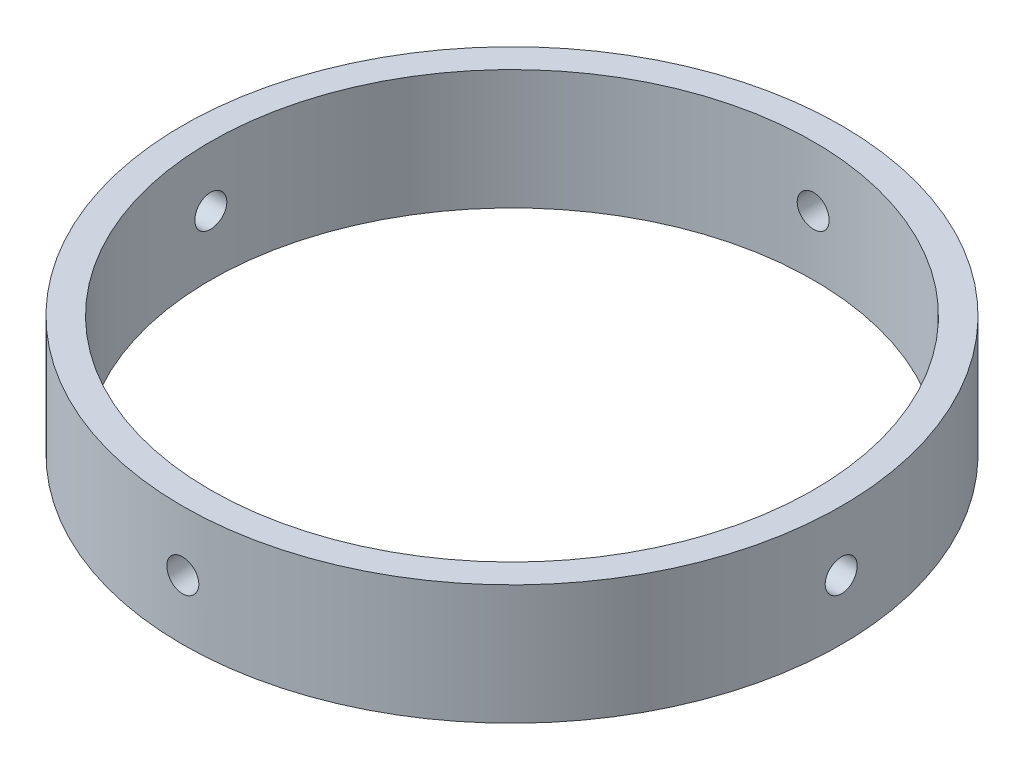
SolidWorks part; units mm, degrees
ref_plane "Front Plane" through (0, 0, 0) normal (0, 0, 1) x (1, 0, 0)
ref_plane "Top Plane" through (0, 0, 0) normal (0, 1, 0) x (1, 0, 0)
ref_plane "Right Plane" through (0, 0, 0) normal (1, 0, 0) x (0, 0, -1)
sketch "Sketch1" plane through (0, 0, 0) normal (0, 1, 0) x (1, 0, 0)
  line L0 (37.75, 0) -> (41.25, 0)
  line L1 (37.75, 0) -> (0, 0) construction
  line L2 (0, 0) -> (38.505, 14.7963) construction
  circle A0 centre (0, 0) radius 37.75
  circle A1 centre (0, 0) radius 41.25
  dimension "D1" = 75.5
  dimension "D2" = 3.5
extrude "Boss-Extrude1" add sketch "Sketch1" along normal blind 15 contours A1 A0 region at (-40.0833, 0, 0)
sketch "Sketch2" plane through (0, 0, 0) normal (1, 0, 0) x (0, 0, -1)
  line L0 (0, 0) -> (0, 15) construction
  line L1 (37.75, 15) -> (-37.75, 15) construction
  circle A0 centre (0, 7.5) radius 2
extrude "Cut-Extrude2" cut sketch "Sketch2" against normal blind 50 and the other way blind 50
sketch "Sketch4" plane through (0, 0, 0) normal (0, 0, 1) x (1, 0, 0)
  line L0 (0, 0) -> (0, 15) construction
  line L1 (41.25, 15) -> (-41.25, 15) construction
  circle A0 centre (0, 7.5) radius 2
extrude "Cut-Extrude3" cut sketch "Sketch4" against normal blind 50 and the other way blind 50
